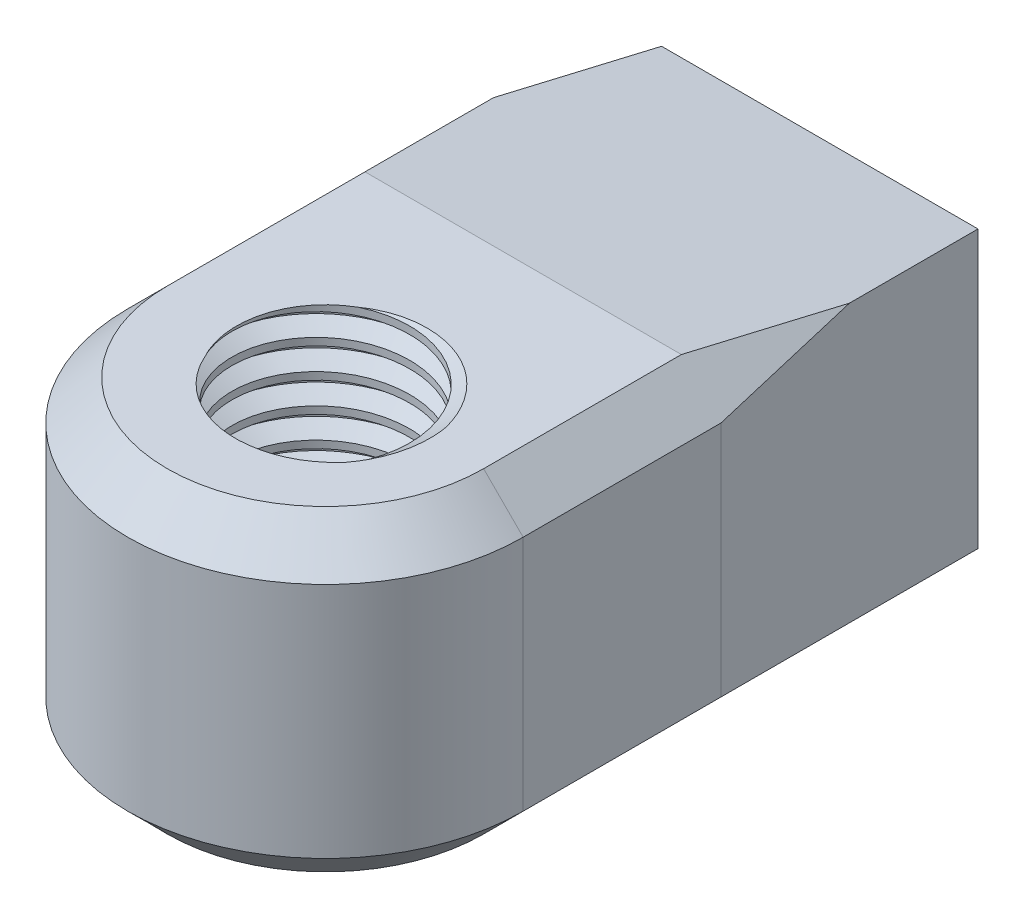
SolidWorks part; units mm, degrees
ref_plane "Front Plane" through (0, 0, 0) normal (0, 0, 1) x (1, 0, 0)
ref_plane "Top Plane" through (0, 0, 0) normal (0, 1, 0) x (1, 0, 0)
ref_plane "Right Plane" through (0, 0, 0) normal (1, 0, 0) x (0, 0, -1)
sketch "Sketch1" plane through (0, 0, 0) normal (0, 1, 0) x (1, 0, 0)
  line L1 (-10, 0) -> (10, 0)
  line L2 (-10, 0) -> (-10, 25)
  line L3 (-10, 25) -> (10, 25)
  line L4 (10, 0) -> (10, 25)
  circle A0 centre (0, 0) radius 4.5
  circle A1 centre (0, 0) radius 10
  dimension "D1" = 9
  dimension "D2" = 20
  dimension "D3" = 25
extrude "Boss-Extrude1" add sketch "Sketch1" along normal blind 16 contours A1 L4 L3 L2 | L1 A1 A0 | L1 A1 A0 region at (0, 0, -4.8368) region at (0, 0, 4.8368) region at (0, 0, -16.2817)
chamfer "Chamfer1" distance 15 distance2 2 3 edges at (10, 8, -25) (-10, 8, -25) (0, 16, -25) first distance on face at (10, 8, -12.5) first distance on face at (-10, 8, -12.5) first distance on face at (0, 16, -10)
sketch "Sketch2" plane through (0, 0, -25) normal (0, 0, -1) x (-1, 0, 0)
  line L0 (8, 0) -> (-8, 0) construction
  line L1 (10, 16) -> (10, 0) construction
  circle A0 centre (0, 8) radius 3
  dimension "D1" = 6
  dimension "D2" = 8
  dimension "D3" = 10
extrude "Cut-Extrude1" cut sketch "Sketch2" against normal blind 15
chamfer "Chamfer2" distance 2 angle 45 6 edges at (0, 0, 10) (-10, 16, -5) (-10, 0, -5) (10, 0, -5) (10, 16, -5) (0, 16, 10)
thread "Thread1" pitch 1.5 method cut profile "Thread Profile1" start angle 0, offset 1, length 0, pitch 1.5, diameter 9
ref_plane "Plane1" through (4.5, -1, 0) normal (0, 0, 1) x (1, 0, 0)
sketch "Thread Profile1" plane through (4.5, -1, 0) normal (0, 0, 1) x (1, 0, 0)
  line L0 (0, 0) -> (0, 1.5) construction
  line L1 (0, 0) -> (0.8119, 0.4687)
  line L2 (0.8119, 0.4687) -> (0.8119, 0.6562)
  line L3 (0.8119, 0.6562) -> (0, 1.125)
  line L4 (0.8119, 0.5625) -> (0, 0.5625) construction
  line L11 (0, 0) -> (0, 1.125)
  point P2 (0, 0)
  dimension "Pitch" = 1.5
  dimension "Profile_Angle" = 60
  dimension "Profile_Land" = 0.1875
  dimension "Profile_Height" = 0.8119
sketch "Sketch3" plane through (0, 0, 0) normal (0, -1, 0) x (1, 0, 0)
  line L0 (-8, -25) -> (8, -25) construction
  circle A0 centre (0.4266, -18) radius 2.25
  dimension "D2" = 4.5
  dimension "D1" = 7
extrude "Cut-Extrude2" cut sketch "Sketch3" against normal up to surface (5.0305 mm away) up to face at (-3, 8, -10)
